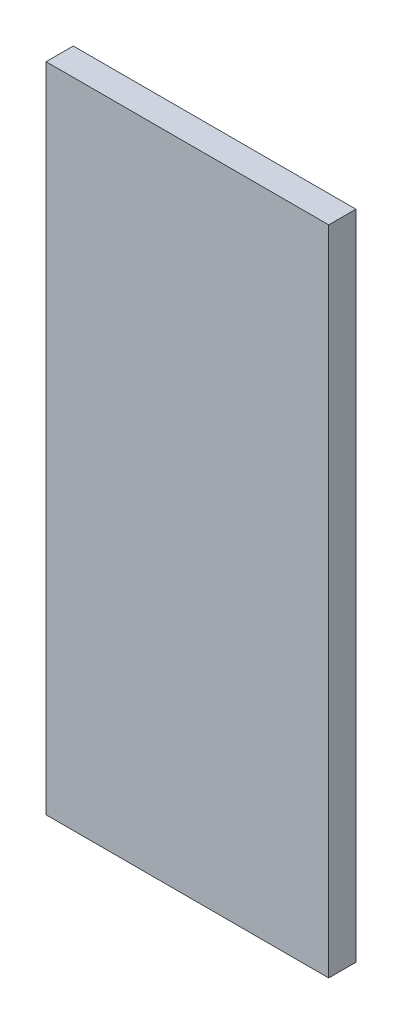
SolidWorks part; units mm, degrees
ref_plane "Front Plane" through (0, 0, 0) normal (0, 0, 1) x (1, 0, 0)
ref_plane "Top Plane" through (0, 0, 0) normal (0, 1, 0) x (1, 0, 0)
ref_plane "Right Plane" through (0, 0, 0) normal (1, 0, 0) x (0, 0, -1)
sketch "Sketch1" plane through (0, 0, 0) normal (0, 0, 1) x (1, 0, 0)
  line L0 (-1364.9405, -40.741) -> (-1364.9405, 111.659) construction
  line L1 (-1397.9605, -40.741) -> (-1331.9205, -40.741)
  line L2 (-1397.9605, -40.741) -> (-1397.9605, 111.659)
  line L3 (-1397.9605, 111.659) -> (-1331.9205, 111.659)
  line L4 (-1331.9205, -40.741) -> (-1331.9205, 111.659)
  line L5 (-1397.9605, -40.741) -> (-1397.9605, 111.659) construction
  line L6 (-1331.9205, 111.659) -> (-1331.9205, -40.741) construction
  dimension "D2" = 152.4
extrude "Boss-Extrude1" add sketch "Sketch1" along normal blind 6.35
